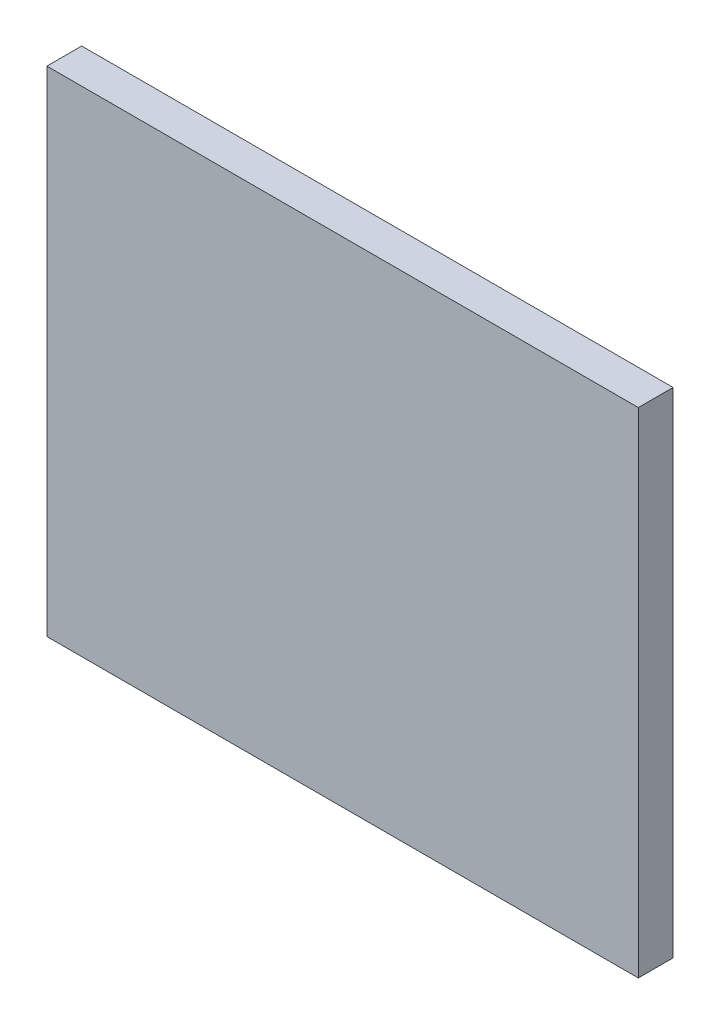
SolidWorks part; units mm, degrees
ref_plane "Front Plane" through (0, 0, 0) normal (0, 0, 1) x (1, 0, 0)
ref_plane "Top Plane" through (0, 0, 0) normal (0, 1, 0) x (1, 0, 0)
ref_plane "Right Plane" through (0, 0, 0) normal (1, 0, 0) x (0, 0, -1)
sketch "Sketch1" plane through (0, 0, 0) normal (0, 0, 1) x (1, 0, 0)
  line L1 (85, -71) -> (-85, -71)
  line L2 (85, -71) -> (85, 71)
  line L3 (85, 71) -> (-85, 71)
  line L4 (-85, -71) -> (-85, 71)
  line L5 (85, -71) -> (-85, 71) construction
  line L6 (85, 71) -> (-85, -71) construction
  point P0 (0, 0)
  dimension "D1" = 170
  dimension "D2" = 142
extrude "Boss-Extrude1" add sketch "Sketch1" along normal mid plane 10
